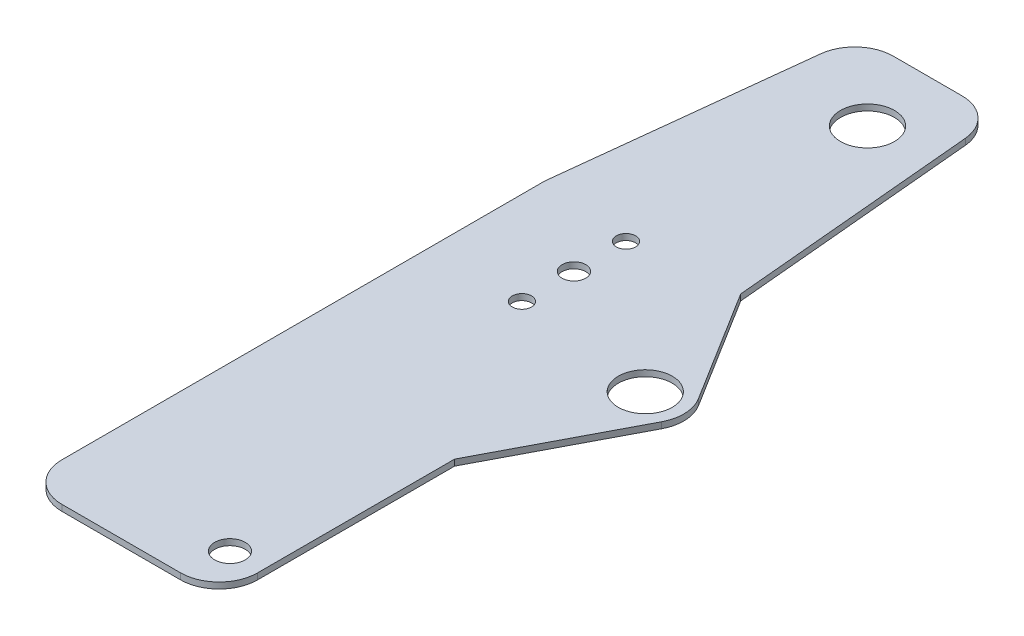
SolidWorks part; units mm, degrees
ref_plane "Front" through (0, 0, 0) normal (0, 0, 1) x (1, 0, 0)
ref_plane "Top" through (0, 0, 0) normal (0, 1, 0) x (1, 0, 0)
ref_plane "Right" through (0, 0, 0) normal (1, 0, 0) x (0, 0, -1)
sketch "Sketch1" plane through (0, 0, 0) normal (0, 1, 0) x (1, 0, 0)
  line L0 (10.4543, 228.6) -> (0, 135.3627)
  line L1 (0, 0) -> (50.8, 0)
  line L2 (0, 0) -> (0, 228.6)
  line L3 (0, 228.6) -> (50.8, 228.6)
  line L4 (50.8, 0) -> (50.8, 228.6)
  line L5 (42.3273, 228.6) -> (50.8, 135.3627)
  line L8 (50.8, 0) -> (24.327, 0)
  line L9 (50.8, 0) -> (50.8, -15)
  line L10 (50.8, -15) -> (24.327, -15)
  line L11 (24.327, 0) -> (24.327, -15)
  line L16 (50.8, 120.6192) -> (50.8, 104.4882)
  line L18 (50.8, 64.8791) -> (50.8, 87.4235)
  circle A3 centre (42.3273, 11.2956) radius 3.9601
  circle A12 centre (60.4, 101.001) radius 10
  circle A13 centre (29.5042, 189.5572) radius 7
  circle A15 centre (24.1018, 118.7849) radius 3.0637
  circle A16 centre (24.1018, 105.2849) radius 2.5
  circle A17 centre (24.1018, 132.2849) radius 2.5
  dimension "D3" = 20
  dimension "D5" = 15
  dimension "D6" = 14
  dimension "D1" = 50.8
  dimension "D2" = 228.6
extrude "Boss-Extrude1" add sketch "Sketch1" along normal blind 1.5875 contours L1 L4 L3 L0 L2 region at (26.3908, 0, -226.2582)
sketch "Sketch4" plane through (0, 0, -228.6) normal (0, 0, -1) x (-1, 0, 0)
  line L1 (-61.3109, 11.9192) -> (4.9615, 11.9192)
  line L2 (-61.3109, 11.9192) -> (-61.3109, -15.8811)
  line L3 (-61.3109, -15.8811) -> (4.9615, -15.8811)
  line L4 (4.9615, 11.9192) -> (4.9615, -15.8811)
extrude "Cut-Extrude2" cut sketch "Sketch4" against normal blind 20
fillet "Fillet3" radius 10 1 edges at (44.1447, 0.7937, -208.6)
fillet "Fillet4" radius 10 3 edges at (50.8, 0.7937, 0) (0, 0.7937, 0) (8.2118, 0.7937, -208.6)
sketch "Sketch6" plane through (0, 1.5875, 0) normal (0, 1, 0) x (1, 0, 0)
  line L0 (68.8909, 106.2834) -> (50.8, 135.3627)
  line L1 (50.8, 135.3627) -> (50.8, 103.801)
  line L2 (69.2582, 96.3607) -> (50.8, 61.1242)
  line L3 (50.8, 10) -> (50.8, 98.201) construction
  line L4 (50.8, 61.1242) -> (50.8, 96.3607)
  line L5 (50.8, 96.3607) -> (50.8, 98.201)
  circle A0 centre (60.4, 101.001) radius 10
  line M4 (50.8, 10) -> (50.8, 98.201)
  arc M5 (50.8, 98.201) -> (50.8, 103.801) centre (60.4, 101.001) cw
  line M6 (50.8, 103.801) -> (50.8, 135.3627)
extrude "Boss-Extrude3" add sketch "Sketch6" against normal blind 1.5875 contours A0 L0 M6 | A0 M5 | A0 L2 M4 region at (55.8248, 1.5875, -118.0301) region at (60.4, 1.5875, -101.001) region at (56.0341, 1.5875, -82.1407)
sketch "Sketch7" plane through (0, 1.5875, 0) normal (0, 1, 0) x (1, 0, 0)
  circle A0 centre (60.4, 101.001) radius 7
  dimension "D1" = 14
extrude "Cut-Extrude3" cut sketch "Sketch7" against normal blind 1.5875
equation "\"7i\"=101.6"
